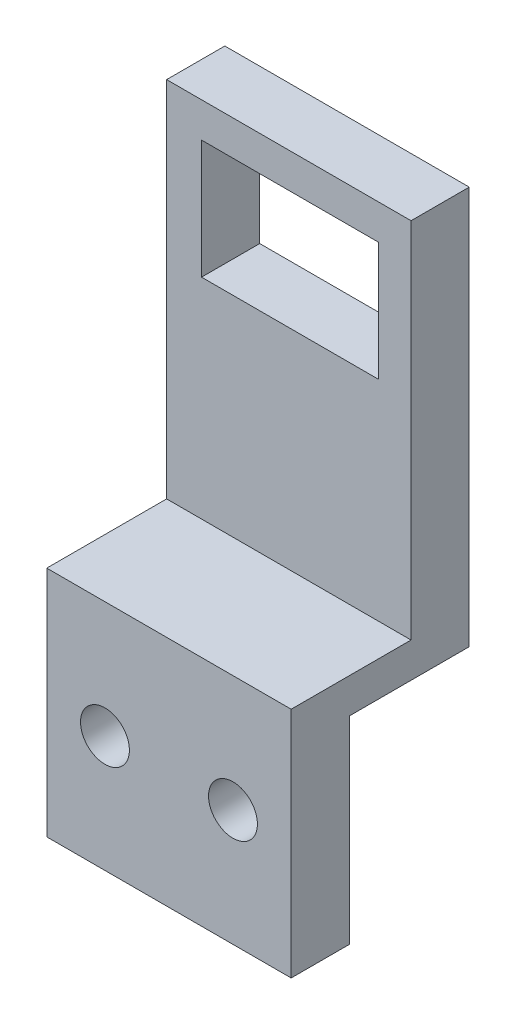
SolidWorks part; units mm, degrees
ref_plane "Front Plane" through (0, 0, 0) normal (0, 0, 1) x (1, 0, 0)
ref_plane "Top Plane" through (0, 0, 0) normal (0, 1, 0) x (1, 0, 0)
ref_plane "Right Plane" through (0, 0, 0) normal (1, 0, 0) x (0, 0, -1)
sketch "Sketch1" plane through (0, 0, 0) normal (0, 0, 1) x (1, 0, 0)
  line L1 (0, 0) -> (21, 0)
  line L2 (0, 0) -> (0, 51.2)
  line L3 (0, 51.2) -> (21, 51.2)
  line L4 (21, 0) -> (21, 51.2)
  line L5 (3, 48.2) -> (18.2, 48.2)
  line L6 (3, 48.2) -> (3, 38)
  line L7 (3, 38) -> (18.2, 38)
  line L8 (18.2, 48.2) -> (18.2, 38)
  circle A0 centre (5, 10) radius 2.1
  circle A1 centre (16, 10) radius 2.1
  dimension "D6" = 4.2
  dimension "D9" = 5
  dimension "D1" = 10.2
  dimension "D2" = 15.2
  dimension "D3" = 21
  dimension "D4" = 3
  dimension "D5" = 3
  dimension "D7" = 10
  dimension "D8" = 10
  dimension "D10" = 5
  dimension "D11" = 38
extrude "Boss-Extrude1" add sketch "Sketch1" along normal blind 15.3
sketch "Sketch2" plane through (0, 0, 0) normal (-1, 0, 0) x (0, 0, 1)
  line L0 (15.3, 51.2) -> (0, 51.2) construction
  line L1 (15.3, 51.2) -> (5, 51.2)
  line L2 (15.3, 51.2) -> (15.3, 20)
  line L3 (15.3, 20) -> (5, 20)
  line L4 (5, 51.2) -> (5, 20)
  line L5 (15.3, 51.2) -> (15.3, 0) construction
  line L6 (0, 51.2) -> (0, 0) construction
  line L7 (0, 0) -> (10.3, 0)
  line L8 (0, 0) -> (0, 17)
  line L9 (0, 17) -> (10.3, 17)
  line L10 (10.3, 0) -> (10.3, 17)
  dimension "D1" = 17
  dimension "D2" = 3
  dimension "D3" = 5
  dimension "D4" = 5
extrude "Cut-Extrude1" cut sketch "Sketch2" against normal blind 21 contours L2 L1 L4 L3 | L8 L7 L10 L9
